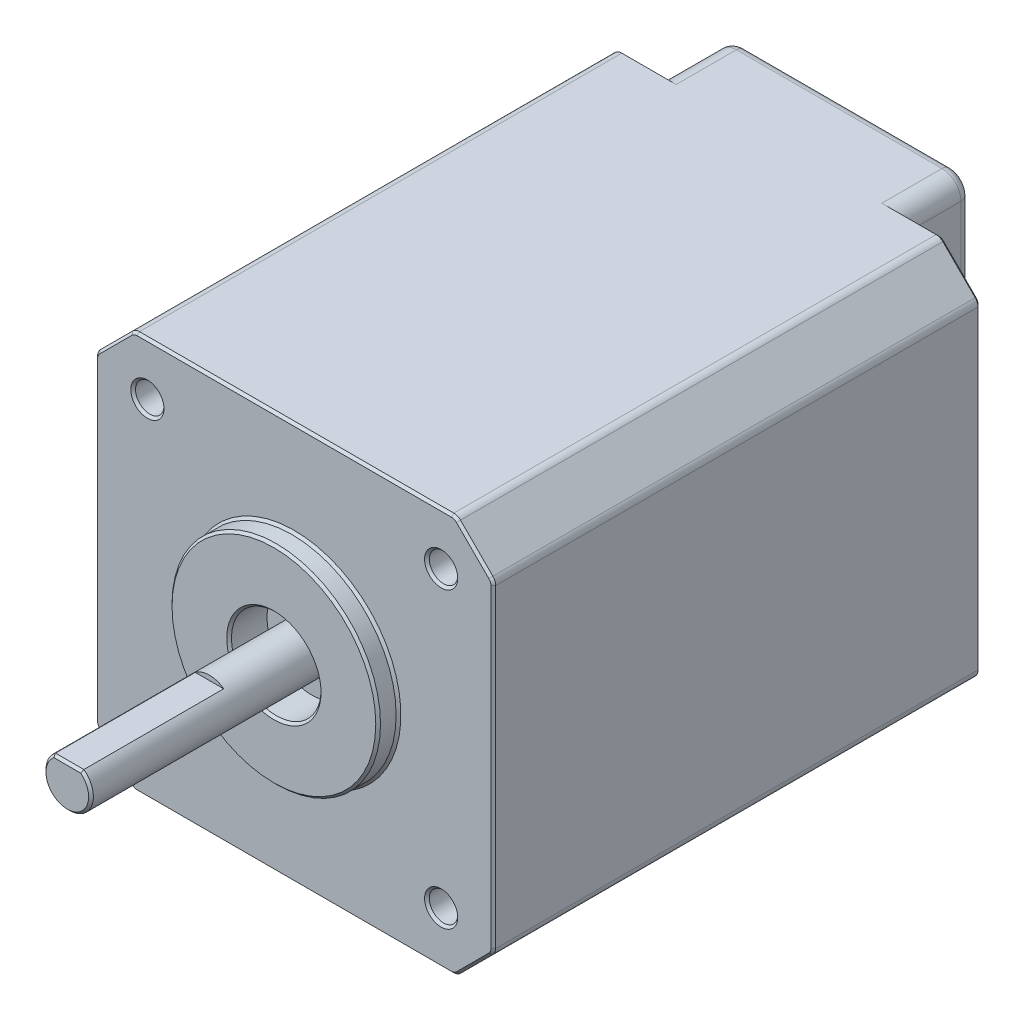
SolidWorks part; units mm, degrees
ref_plane "Front Plane" through (0, 0, 0) normal (0, 0, 1) x (1, 0, 0)
ref_plane "Top Plane" through (0, 0, 0) normal (0, 1, 0) x (1, 0, 0)
ref_plane "Right Plane" through (0, 0, 0) normal (1, 0, 0) x (0, 0, -1)
sketch "Sketch1" plane through (0, 0, 0) normal (0, 0, 1) x (1, 0, 0)
  line L0 (-21, 17) -> (-17, 21)
  line L1 (-17, 21) -> (17, 21)
  line L2 (-21, 17) -> (-21, -17)
  line L3 (-17, -21) -> (17, -21)
  line L4 (21, 17) -> (21, -17)
  line L5 (-21, 21) -> (21, -21) construction
  line L6 (-21, -21) -> (21, 21) construction
  line L7 (17, 21) -> (21, 17)
  line L8 (17, -21) -> (21, -17)
  line L9 (-21, -17) -> (-17, -21)
  point P0 (0, 0)
  dimension "D1" = 42
extrude "Boss-Extrude1" add sketch "Sketch1" against normal blind 51.4
sketch "Sketch2" plane through (0, 0, 0) normal (0, 0, 1) x (1, 0, 0)
  line L0 (-4.338, 0) -> (4.614, 0) construction
  line L1 (0, 6.6252) -> (0, -4.0225) construction
  line L2 (-15.5, 15.5) -> (15.5, 15.5) construction
  line L3 (-15.5, 15.5) -> (-15.5, -15.5) construction
  circle A0 centre (-15.5, 15.5) radius 1.5
  circle A1 centre (15.5, 15.5) radius 1.5
  circle A2 centre (15.5, -15.5) radius 1.5
  circle A3 centre (-15.5, -15.5) radius 1.5
  dimension "D1" = 3
  dimension "D2" = 31
extrude "Cut-Extrude1" cut sketch "Sketch2" against normal blind 4.5
sketch "Sketch3" plane through (0, 0, 0) normal (0, 0, 1) x (1, 0, 0)
  circle A0 centre (0, 0) radius 11
  dimension "D1" = 22
extrude "Boss-Extrude2" add sketch "Sketch3" along normal blind 2.15
sketch "Sketch5" plane through (0, 0, 2.15) normal (0, 0, 1) x (1, 0, 0)
  circle A0 centre (0, 0) radius 4.725
  dimension "D1" = 9.45
extrude "Cut-Extrude2" cut sketch "Sketch5" against normal blind 4
sketch "Sketch4" plane through (0, 0, -1.85) normal (0, 0, 1) x (1, 0, 0)
  circle A0 centre (0, 0) radius 2.5
  dimension "D1" = 5
extrude "Boss-Extrude3" add sketch "Sketch4" along normal offset from surface (25.8 mm away) 21.8 up to face at (4.725, 0, 2.15) offset beyond the face yes
sketch "Sketch6" plane through (0, 0, 23.95) normal (0, 0, 1) x (1, 0, 0)
  line L0 (-1.5, 2) -> (1.5, 2)
  circle A1 centre (0, 0) radius 2.5
  arc A2 (1.5, 2) -> (-1.5, 2) centre (0, 0) ccw
  point P5 (0, -2.5)
  dimension "D2" = 4.5
  dimension "D1" = 0
extrude "Cut-Extrude3" cut sketch "Sketch6" against normal blind 15
sketch "Sketch7" plane through (0, 0, -51.4) normal (0, 0, -1) x (-1, 0, 0)
  line L0 (0, 11.9885) -> (0, -5.521) construction
  line L1 (-17, 21) -> (17, 21) construction
  line L2 (-12.85, 7.1) -> (12.85, 7.1)
  line L3 (-12.85, 7.1) -> (-12.85, 21)
  line L4 (-12.85, 21) -> (12.85, 21)
  line L5 (12.85, 7.1) -> (12.85, 21)
  line L6 (-12.85, 7.1) -> (12.85, 21) construction
  line L7 (-12.85, 21) -> (12.85, 7.1) construction
  point P1 (0, 14.05)
  dimension "D1" = 25.7
  dimension "D2" = 13.9
extrude "Boss-Extrude4" add sketch "Sketch7" along normal offset from surface (7.1 mm away) 58.5 up to face at (11, 0, 0)
fillet "Fillet1" radius 1 12 edges at (17, 21, -25.7) (21, 17, -25.7) (21, -17, -25.7) (17, -21, -25.7) (-17, -21, -25.7) (-21, -17, -25.7) (-17, 21, -25.7) (-21, 17, -25.7) (12.85, 14.05, -58.5) (0, 21, -58.5) (-12.85, 14.05, -58.5) (0, 7.1, -58.5)
fillet "Fillet2" radius 2 8 edges at (12.85, 7.1, -54.45) (12.85, 21, -54.45) (-12.85, 7.1, -54.45) (-12.85, 21, -54.45) (-12.5571, 20.7071, -58.2071) (-12.5571, 7.3929, -58.2071) (12.5571, 20.7071, -58.2071) (12.5571, 7.3929, -58.2071)
chamfer "Chamfer1" distance 0.25 angle 45 42 edges at (0, -2.5, 23.95) (0, 2, 23.95) (11, 0, 2.15) (4.725, 0, 2.15) (20.9239, 16.9685, 0) (21, 0, 0) (20.9239, -16.9685, 0) (19, -19, 0) (16.9685, -20.9239, 0) (0, -21, 0) (-16.9685, -20.9239, 0) (-19, -19, 0) (-20.9239, -16.9685, 0) (-21, 0, 0) (-20.9239, 16.9685, 0) (-19, 19, 0) (-16.9685, 20.9239, 0) (0, 21, 0) (16.9685, 20.9239, 0) (19, 19, 0) (-14, 15.5, 0) (14, 15.5, 0) (17, -15.5, 0) (-17, -15.5, 0) (11, 0, 0) (13.7179, 21, -51.4) (16.9685, 20.9239, -51.4) (19, 19, -51.4) (20.9239, 16.9685, -51.4) (21, 0, -51.4) (20.9239, -16.9685, -51.4) (19, -19, -51.4) (16.9685, -20.9239, -51.4) (-13.7179, 21, -51.4) (0, -21, -51.4) (-16.9685, 20.9239, -51.4) (-16.9685, -20.9239, -51.4) (-19, 19, -51.4) (-19, -19, -51.4) (-20.9239, 16.9685, -51.4) (-20.9239, -16.9685, -51.4) (-21, 0, -51.4)
